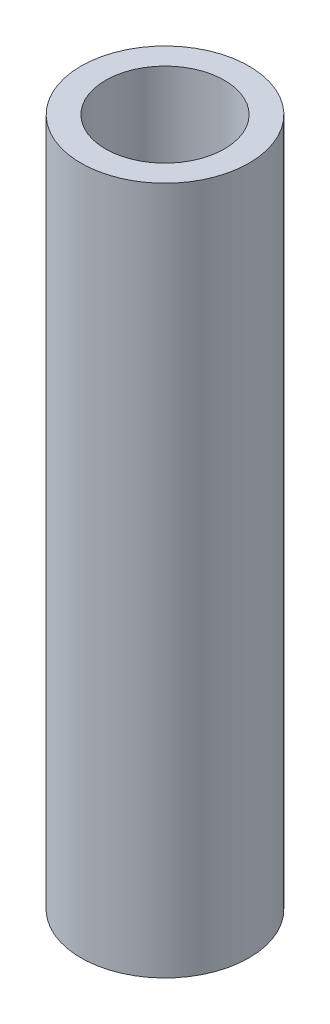
SolidWorks part; units mm, degrees
material "Rubber"
ref_plane "Front Plane" through (0, 0, 0) normal (0, 0, 1) x (1, 0, 0)
ref_plane "Top Plane" through (0, 0, 0) normal (0, 1, 0) x (1, 0, 0)
ref_plane "Right Plane" through (0, 0, 0) normal (1, 0, 0) x (0, 0, -1)
sketch "Sketch1" plane through (0, 0, 0) normal (0, 1, 0) x (1, 0, 0)
  circle A0 centre (0, 0) radius 6.05
extrude "Extrude-Thin1" add sketch "Sketch1" along normal blind 70 thin thin type one direction wall 2.5
